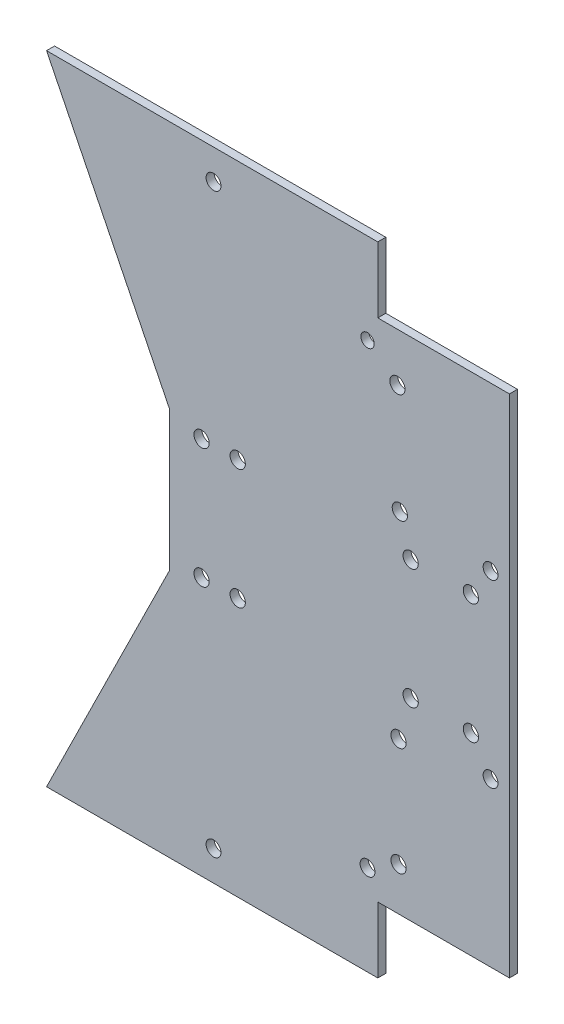
SolidWorks part; units mm, degrees
material "Thornel Mat VMA"
ref_plane "Front Plane" through (0, 0, 0) normal (0, 0, 1) x (1, 0, 0)
ref_plane "Top Plane" through (0, 0, 0) normal (0, 1, 0) x (1, 0, 0)
ref_plane "Right Plane" through (0, 0, 0) normal (1, 0, 0) x (0, 0, -1)
sketch "Sketch2" plane through (0, 0, 0) normal (0, 0, 1) x (-1, 0, 0)
  line L11 (-2.9301, 168.7083) -> (38.7094, 168.7083)
  line L12 (-2.9301, 8.6883) -> (38.7094, 8.6883)
  line L13 (38.7094, -12.1397) -> (38.7094, 8.6883)
  line L14 (143.4971, -12.1397) -> (38.7094, -12.1397)
  line L15 (38.7094, 189.5363) -> (38.7094, 168.7083)
  line L16 (143.4971, 189.5363) -> (38.7094, 189.5363)
  line L17 (104.6174, 110.8598) -> (143.4971, 189.5363)
  line L18 (104.6174, 66.5368) -> (143.4971, -12.1397)
  line L19 (104.6174, 66.5368) -> (72.8674, 66.5368)
  line L20 (72.8674, 66.5368) -> (72.8674, 110.8598)
  line L21 (104.6174, 110.8598) -> (72.8674, 110.8598)
  line L22 (-2.9301, 168.7083) -> (-2.9301, 8.6883)
  line L23 (41.9566, 19.6103) -> (41.9566, 13.2603) construction
  circle A0 centre (41.9566, 160.9613) radius 2.3495
  circle A1 centre (90.6739, 180.0113) radius 2.3495
  circle A2 centre (90.6739, -2.6147) radius 2.3495
  circle A3 centre (3.0351, 117.2098) radius 2.3495
  circle A4 centre (3.0351, 60.1868) radius 2.3495
  circle A5 centre (41.9566, 16.4353) radius 2.0955
  point P36 (41.9566, 16.4353)
  dimension "D3" = 4.699
  dimension "D7" = 31.75
  dimension "D8" = 41.6395
  dimension "D9" = 20.828
  dimension "D10" = 160.02
  dimension "D11" = 20.828
  dimension "D12" = 41.6395
  dimension "D13" = 104.7876
  dimension "D14" = 116.297
  dimension "D15" = 116.297
  dimension "D16" = 44.323
  dimension "D17" = 26.297
  dimension "D18" = 9.525
  dimension "D19" = 28.575
  dimension "D20" = 7.747
  dimension "D21" = 51.9645
  dimension "D22" = 51.4985
  dimension "D23" = 5.9651
  dimension "D24" = 51.4985
  dimension "D25" = 5.9651
  dimension "D26" = 7.747
  dimension "D27" = 3.2471
  dimension "D28" = 9.525
  dimension "D29" = 51.9645
extrude "Boss-Extrude1" add sketch "Sketch2" along normal blind 2.54
sketch "Sketch3" plane through (0, 0, 2.54) normal (0, 0, 1) x (1, 0, 0)
  line L1 (-104.6174, -66.5368) -> (-72.8674, -66.5368)
  line L2 (-104.6174, -66.5368) -> (-104.6174, -110.8598)
  line L3 (-104.6174, -110.8598) -> (-72.8674, -110.8598)
  line L4 (-72.8674, -66.5368) -> (-72.8674, -110.8598)
extrude "Boss-Extrude2" add sketch "Sketch3" against normal up to surface (2.54 mm away) up to face at (-65.9118, -88.6983, 0)
sketch "Sketch4" plane through (0, 0, 2.54) normal (0, 0, 1) x (1, 0, 0)
  line L0 (-104.6174, -66.5368) -> (-104.6174, -72.8868)
  line L1 (-104.6174, -66.5368) -> (-104.6174, -110.8598) construction
  line L2 (-104.6174, -69.7118) -> (2.9301, -69.7118) construction
  line L3 (2.9301, -168.7083) -> (2.9301, -8.6883) construction
  line L4 (-104.6174, -88.6983) -> (2.9301, -88.6983) construction
  line L5 (-104.6174, -107.6848) -> (2.9301, -107.6848) construction
  line L6 (-104.6174, -110.8598) -> (-104.6174, -104.5098)
  circle A0 centre (-94.4574, -69.7118) radius 2.413
  circle A1 centre (-83.0274, -69.7118) radius 2.413
  circle A2 centre (-28.3119, -69.7118) radius 2.413
  circle A3 centre (-9.2619, -69.7118) radius 2.413
  circle A4 centre (-9.2619, -107.6848) radius 2.413
  circle A5 centre (-28.3119, -107.6848) radius 2.413
  circle A6 centre (-83.0274, -107.6848) radius 2.413
  circle A7 centre (-94.4574, -107.6848) radius 2.413
  dimension "D2" = 10.16
  dimension "D4" = 4.826
  dimension "D5" = 4.826
  dimension "D8" = 4.826
  dimension "D9" = 4.826
  dimension "D1" = 3.175
  dimension "D3" = 11.43
  dimension "D6" = 19.05
  dimension "D7" = 12.192
extrude "Cut-Extrude1" cut sketch "Sketch4" against normal through all contours A0 | A1 | A2 | A3 | A4 | A5 | A6 | A7
sketch "Sketch5" plane through (0, 0, 2.54) normal (0, 0, 1) x (1, 0, 0)
  circle A0 centre (-31.739, -58.2731) radius 2.413
  dimension "D1" = 4.826
sketch "Sketch6" plane through (0, 0, 2.54) normal (0, 0, 1) x (1, 0, 0)
  circle A0 centre (-32.5114, -23.9918) radius 2.413
  dimension "D1" = 4.826
extrude "Cut-Extrude2" cut sketch "Sketch5" against normal through all
extrude "Cut-Extrude3" cut sketch "Sketch6" against normal through all
sketch "Sketch7" plane through (0, 0, 2.54) normal (0, 0, 1) x (1, 0, 0)
  circle A0 centre (-32.1405, -155.0714) radius 2.413
  circle A1 centre (-32.1405, -120.7814) radius 2.413
  dimension "D1" = 4.826
  dimension "D2" = 4.826
extrude "Cut-Extrude4" cut sketch "Sketch7" against normal through all
